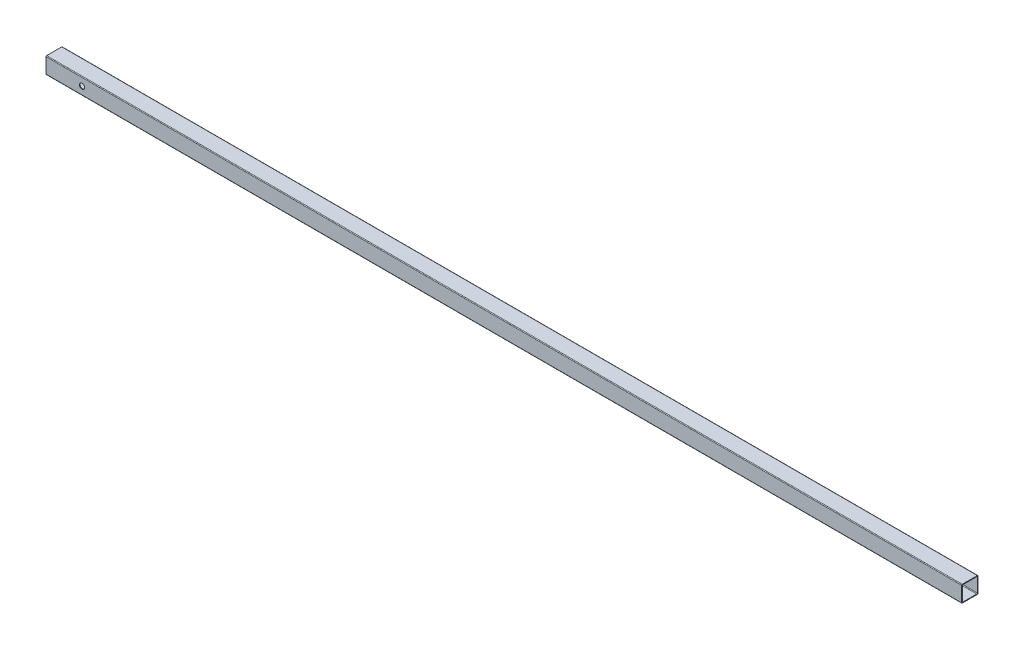
SolidWorks part; units mm, degrees
material "Thornel Mat VMA"
ref_plane "Front Plane" through (0, 0, 0) normal (0, 0, 1) x (1, 0, 0)
ref_plane "Top Plane" through (0, 0, 0) normal (0, 1, 0) x (1, 0, 0)
ref_plane "Right Plane" through (0, 0, 0) normal (1, 0, 0) x (0, 0, -1)
sketch "Sketch2" plane through (0, 0, 0) normal (1, 0, 0) x (0, 0, -1)
  line L1 (0.762, 0) -> (18.288, 0)
  line L2 (0, 0.762) -> (0, 18.288)
  line L3 (0.762, 19.05) -> (18.288, 19.05)
  line L4 (19.05, 0.762) -> (19.05, 18.288)
  line L5 (1.524, 0.762) -> (17.526, 0.762)
  line L6 (0.762, 1.524) -> (0.762, 17.526)
  line L7 (1.524, 18.288) -> (17.526, 18.288)
  line L8 (18.288, 1.524) -> (18.288, 17.526)
  arc A0 (17.526, 18.288) -> (18.288, 17.526) centre (17.526, 17.526) cw
  arc A1 (17.526, 0.762) -> (18.288, 1.524) centre (17.526, 1.524) ccw
  arc A2 (1.524, 0.762) -> (0.762, 1.524) centre (1.524, 1.524) cw
  arc A3 (0.762, 17.526) -> (1.524, 18.288) centre (1.524, 17.526) cw
  arc A4 (18.288, 19.05) -> (19.05, 18.288) centre (18.288, 18.288) cw
  arc A5 (18.288, 0) -> (19.05, 0.762) centre (18.288, 0.762) ccw
  arc A6 (0.762, 0) -> (0, 0.762) centre (0.762, 0.762) cw
  arc A7 (0, 18.288) -> (0.762, 19.05) centre (0.762, 18.288) cw
  point P11 (18.288, 18.288)
  point P14 (18.288, 0.762)
  point P19 (0.762, 18.288)
  point P22 (19.05, 19.05)
  point P25 (19.05, 0)
  point P28 (0, 0)
  point P31 (0, 19.05)
  dimension "D7" = 0.762
  dimension "D1" = 19.05
  dimension "D2" = 19.05
  dimension "D5" = 0.762
  dimension "D6" = 0.762
  dimension "D3" = 0.762
  dimension "D4" = 0.762
extrude "Boss-Extrude1" add sketch "Sketch2" along normal blind 609.6
sketch "Sketch3" plane through (0, 0, 0) normal (0, 0, 1) x (1, 0, 0)
  line L0 (0, 18.288) -> (0, 0.762) construction
  line L1 (609.6, 19.05) -> (0, 19.05) construction
  circle A0 centre (41.91, 9.525) radius 3.048
  dimension "D1" = 6.096
  dimension "D2" = 41.91
  dimension "D3" = 9.525
extrude "Cut-Extrude1" cut sketch "Sketch3" against normal up to surface (19.05 mm away) up to face at (304.8, 9.525, -19.05)
sketch "Sketch4" plane through (609.6, 0, 0) normal (1, 0, 0) x (0, 0, -1)
  line L1 (0, 12.573) -> (0, 6.477)
  line L2 (0, 12.573) -> (0, 6.477)
  line L6 (19.05, 0.762) -> (19.05, 18.288)
  line L7 (0.762, 0) -> (18.288, 0)
  line L8 (0, 18.288) -> (0, 0.762)
  line L9 (18.288, 19.05) -> (0.762, 19.05)
  line L10 (19.05, 0.762) -> (19.05, 18.288)
  line L11 (0.762, 0) -> (18.288, 0)
  line L12 (0, 18.288) -> (0, 0.762)
  line L13 (18.288, 19.05) -> (0.762, 19.05)
  arc A4 (19.05, 18.288) -> (18.288, 19.05) centre (18.288, 18.288) ccw
  arc A5 (18.288, 0) -> (19.05, 0.762) centre (18.288, 0.762) ccw
  arc A6 (0, 0.762) -> (0.762, 0) centre (0.762, 0.762) ccw
  arc A7 (0.762, 19.05) -> (0, 18.288) centre (0.762, 18.288) ccw
  arc A8 (19.05, 18.288) -> (18.288, 19.05) centre (18.288, 18.288) ccw
  arc A9 (18.288, 0) -> (19.05, 0.762) centre (18.288, 0.762) ccw
  arc A10 (0, 0.762) -> (0.762, 0) centre (0.762, 0.762) ccw
  arc A11 (0.762, 19.05) -> (0, 18.288) centre (0.762, 18.288) ccw
  arc M10 (19.05, 18.288) -> (18.288, 19.05) centre (18.288, 18.288) ccw
  line M11 (18.288, 19.05) -> (0.762, 19.05)
  arc M12 (0.762, 19.05) -> (0, 18.288) centre (0.762, 18.288) ccw
  line M13 (0, 18.288) -> (0, 0.762)
  arc M14 (0, 0.762) -> (0.762, 0) centre (0.762, 0.762) ccw
  line M15 (0.762, 0) -> (18.288, 0)
  arc M16 (18.288, 0) -> (19.05, 0.762) centre (18.288, 0.762) ccw
  line M17 (19.05, 0.762) -> (19.05, 18.288)
  arc M18 (17.526, 18.288) -> (18.288, 17.526) centre (17.526, 17.526) cw
  line M19 (18.288, 17.526) -> (18.288, 1.524)
  arc M20 (18.288, 1.524) -> (17.526, 0.762) centre (17.526, 1.524) cw
  line M21 (17.526, 0.762) -> (1.524, 0.762)
  arc M22 (1.524, 0.762) -> (0.762, 1.524) centre (1.524, 1.524) cw
  line M23 (0.762, 1.524) -> (0.762, 17.526)
  arc M24 (0.762, 17.526) -> (1.524, 18.288) centre (1.524, 17.526) cw
  line M25 (1.524, 18.288) -> (17.526, 18.288)
  dimension "D1" = 0
  dimension "D2" = 0
extrude "Boss-Extrude2" add sketch "Sketch4" along normal blind 457.2 contours M17 M10 M11 M12 M13 M14 M15 M16 M25 M18 M19 M20 M21 M22 M23 M24 region at (609.6, 15.4305, -0.2694)
equation "\"shaft\"=0.75"
equation "\"D1@Sketch2\"=\"shaft\""
equation "\"D2@Sketch2\"=\"shaft\""
equation "\"IDshaft\"=0.4375"
equation "\"D3@Sketch3\"=\"shaft\"/2"
